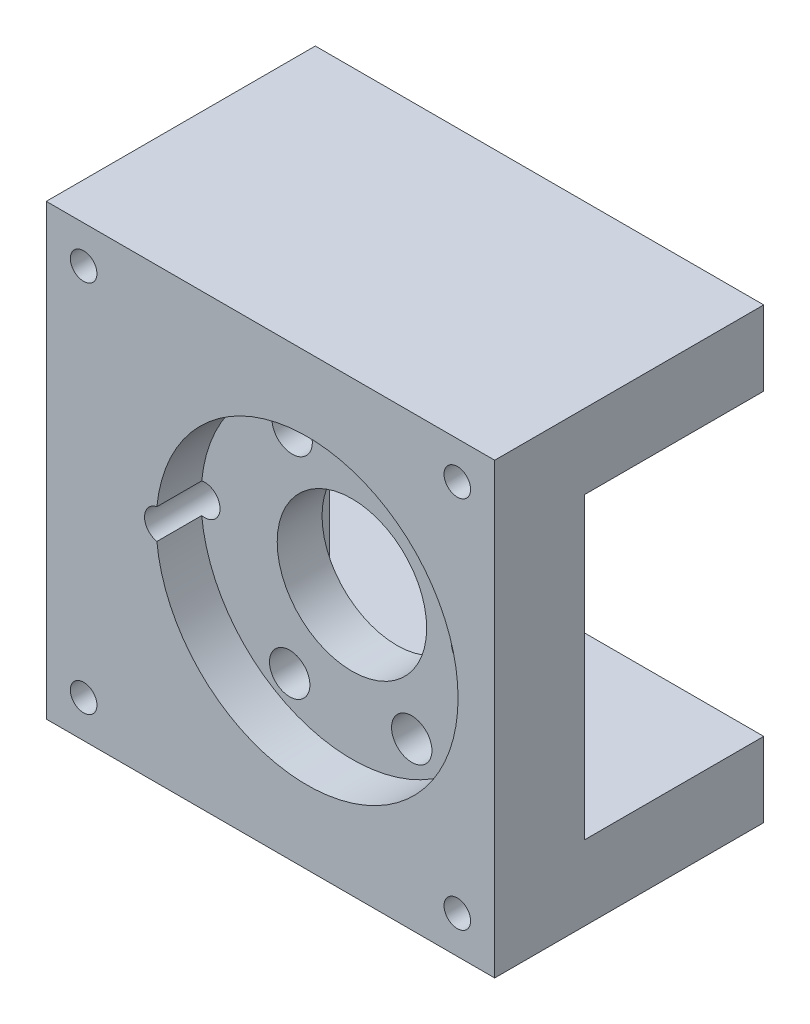
SolidWorks part; units mm, degrees
material "6061-T6 (SS)"
ref_plane "Front Plane" through (0, 0, 0) normal (0, 0, 1) x (1, 0, 0)
ref_plane "Top Plane" through (0, 0, 0) normal (0, 1, 0) x (1, 0, 0)
ref_plane "Right Plane" through (0, 0, 0) normal (1, 0, 0) x (0, 0, -1)
sketch "Sketch2" plane through (0, 0, 0) normal (0, 0, 1) x (1, 0, 0)
  line L0 (0, 0) -> (7.6, 0) construction
  line L1 (7.6, 0) -> (17.45, 0) construction
  line L2 (17.45, -5) -> (30, -5)
  line L3 (0, -15) -> (30, -15)
  line L4 (0, -15) -> (0, 15)
  line L5 (0, 15) -> (30, 15)
  line L6 (30, -15) -> (30, 15)
  line L11 (17.45, 5) -> (30, 5)
  circle A0 centre (7.6, 0) radius 1.025
  circle A1 centre (17.45, 0) radius 5
  dimension "D5" = 2.05
  dimension "D6" = 10
  dimension "D1" = 30
  dimension "D2" = 30
  dimension "D3" = 7.6
  dimension "D4" = 9.85
extrude "Boss-Extrude1" add sketch "Sketch2" along normal blind 18 contours L3 L6 L5 L4 A1 A0 | A1 L2 L6 L11 region at (25.6163, 0, 0) region at (23.725, -5.4243, 0)
sketch "Sketch3" plane through (0, 0, 0) normal (0, 0, -1) x (-1, 0, 0)
  line L0 (6.8, 0) -> (-7.6, 0) construction
  line L2 (-30, 10) -> (0, 10)
  line L3 (-30, 10) -> (-30, -10)
  line L4 (-30, -10) -> (0, -10)
  line L5 (0, 10) -> (0, -10)
  line L6 (0, 15) -> (-30, 15) construction
  line L7 (0, -15) -> (-30, -15) construction
  line L8 (0, -15) -> (0, 15) construction
  line L9 (-30, -15) -> (-30, 15) construction
  circle A0 centre (6.8, 0) radius 12.5 construction
  dimension "D4" = 25
  dimension "D1" = 14.4
  dimension "D2" = 5
  dimension "D3" = 5
extrude "Cut-Extrude1" cut sketch "Sketch3" against normal blind 9
chamfer "Chamfer1" [suppressed] distance 1.5 angle 45
hole_wizard "#2-56 Tapped Hole1" positions "Sketch6" profile "Sketch5" tap size "#2-56" standard "ANSI Inch" end condition through all
sketch "Sketch6" plane through (0, 0, 0) normal (0, 0, -1) x (-1, 0, 0)
  line L0 (-27.5, -12.5) -> (-27.5, 12.5) construction
  line L1 (-27.5, 12.5) -> (-2.5, 12.5) construction
  line L2 (-2.5, 12.5) -> (-2.5, -12.5) construction
  line L3 (-2.5, -12.5) -> (-27.5, -12.5) construction
  line L6 (0, 15) -> (-30, 15) construction
  line L7 (0, -15) -> (-30, -15) construction
  line L8 (-30, 10) -> (-30, 15) construction
  point P0 (-27.5, 12.5)
  point P2 (-27.5, -12.5)
  point P4 (-2.5, -12.5)
  point P6 (-2.5, 12.5)
  dimension "D1" = 2.5
  dimension "D2" = 25
  dimension "D3" = 2.5
  dimension "D4" = 2.5
sketch "Sketch5" plane through (27.5, 12.5, 0) normal (1, 0, 0) x (0, 1, 0)
  line L0 (0, 0) -> (0, 18)
  line L1 (0, 18) -> (0.889, 18)
  line L2 (0.889, 18) -> (0.889, 0)
  line L5 (0.889, 0) -> (0, 0)
  line L11 (0, -6.35) -> (0, 107.95) construction
  dimension "Thru Tap Drill Dia." = 1.778
  dimension "Thru Tap Drill Depth" = 18
cosmetic thread "Hole Thread1" parameters "D2"=2.1844
cosmetic thread "Hole Thread2" parameters "D2"=2.1844
cosmetic thread "Hole Thread3" parameters "D2"=2.1844
cosmetic thread "Hole Thread4" parameters "D2"=2.1844
sketch "Sketch8" plane through (0, 0, 18) normal (0, 0, 1) x (1, 0, 0)
  line L0 (17.45, 10.1) -> (30, 10.1)
  line L2 (17.45, -10.1) -> (30, -10.1)
  line L3 (30, -10.1) -> (30, 10.1)
  line L4 (30, -15) -> (30, 15) construction
  circle A0 centre (17.45, 0) radius 10.1
  circle M6 centre (17.45, 0) radius 5
  circle M7 centre (7.6, 0) radius 1.025
  dimension "D1" = 20.2
extrude "Cut-Extrude2" cut sketch "Sketch8" against normal offset from surface (3 mm away) 15 contours A0 M7 M6 region at (24.39, 6.94, 18) up to face at (26.611, 12.5, 0)
sketch "Sketch9" plane through (0, 0, 9) normal (0, 0, -1) x (-1, 0, 0)
  circle A0 centre (-7.6, 0) radius 2
  circle A1 centre (-7.6, 0) radius 1.025 construction
  circle A2 centre (-7.6, 0) radius 1.025
  dimension "D1" = 4
extrude "Boss-Extrude2" add sketch "Sketch9" along normal offset from surface (0.4 mm away) 8.6 up to face at (26.611, 12.5, 0)
sketch "Sketch10" plane through (0, 0, 9) normal (0, 0, -1) x (-1, 0, 0)
  line L2 (-30, 10) -> (-9.95, 10)
  line L4 (-30, 10) -> (-30, -10)
  line L5 (-30, -10) -> (-9.95, -10)
  line L6 (-9.95, 10) -> (-9.95, -10)
  line L7 (-30, 10) -> (-30, -10) construction
  line L8 (0, 10) -> (-30, 10) construction
  line L9 (-30, -10) -> (0, -10) construction
  circle A0 centre (-17.45, 0) radius 5 construction
  circle M2 centre (-17.45, 0) radius 5
  line M4 (-30, 10) -> (-30, -10)
  line M10 (-30, 10) -> (-30, -10)
  dimension "D1" = 7.5
extrude "Cut-Extrude3" cut sketch "Sketch10" against normal offset from surface (3 mm away) 12 contours M4 | M10 | M2 region at (19.975, 9.7168, 9) up to face at (26.611, 12.5, 0)
fillet "Fillet1" radius 3.302 2 edges at (9.95, -10, 10.5) (9.95, 10, 10.5)
hole_wizard "M2.5 Clearance Hole1" positions "Sketch12" profile "Sketch11" hole size "M2.5" standard "ANSI Metric" end condition through all
sketch "Sketch12" plane through (0, 0, 12) normal (0, 0, -1) x (-1, 0, 0)
  line L0 (-21.45, -6.9282) -> (-13.45, 6.9282) construction
  line L2 (-21.45, 6.9282) -> (-17.45, 0) construction
  line L3 (-17.45, 0) -> (-13.2857, -7.2127) construction
  line L5 (-17.45, 0) -> (-17.45, 6.9282) construction
  line L6 (-17.45, 6.9282) -> (-21.45, 6.9282) construction
  line L8 (-17.45, 6.9282) -> (-13.45, 6.9282) construction
  line L9 (-25.45, 0) -> (-17.45, 0) construction
  point P0 (-21.45, 6.9282)
  point P2 (-13.45, 6.9282)
  point P4 (-13.2857, -7.2127)
  point P6 (-21.45, -6.9282)
  point P33 (-25.45, 0)
  dimension "D1" = 60
  dimension "D2" = 16
  dimension "D3" = 8
sketch "Sketch11" plane through (21.45, 6.9282, 12) normal (1, 0, 0) x (0, 1, 0)
  line L0 (0, 0) -> (0, 6)
  line L1 (0, 6) -> (1.35, 6)
  line L2 (1.35, 6) -> (1.35, 0)
  line L5 (1.35, 0) -> (0, 0)
  line L11 (0, -6.35) -> (0, 107.95) construction
  dimension "Thru Hole Dia." = 2.7
  dimension "Thru Hole Depth" = 6
